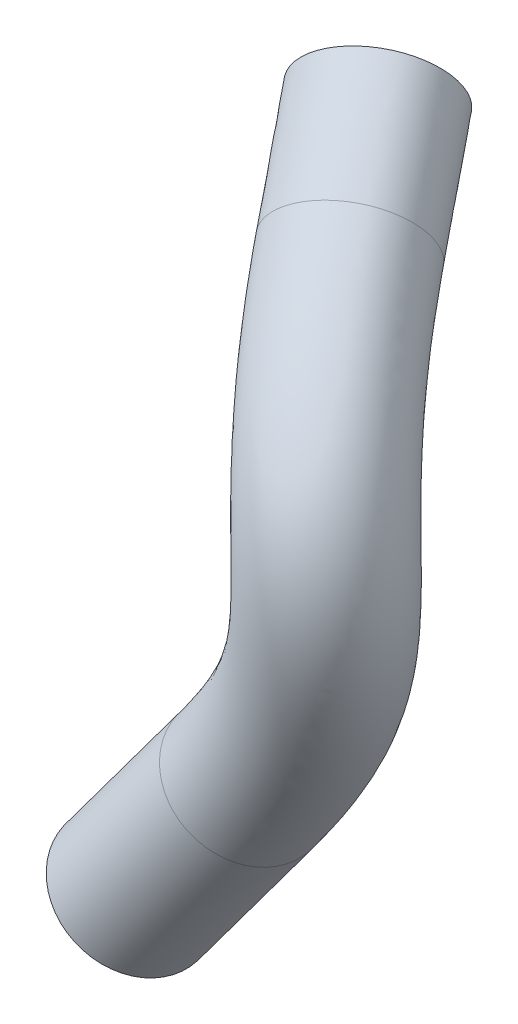
SolidWorks part; units mm, degrees
material "Silicon Rubber"
ref_plane "X-Y Datum" through (0, 0, 0) normal (0, 0, 1) x (1, 0, 0)
ref_plane "X-Z Datum" through (0, 0, 0) normal (0, 1, 0) x (1, 0, 0)
ref_plane "Y-Z Datum" through (0, 0, 0) normal (1, 0, 0) x (0, 0, -1)
sketch3d "3DSketch1"
  line L0 (202.8177, 305.3534, 24.6391) -> (225.5353, 335.9397, 24.6391)
  line L1 (229.5407, 421.9495, 7.7474) -> (216.3328, 432.7155, -11.0889)
  line L2 (229.5407, 421.9495, 7.7474) -> (216.3328, 432.7155, -11.0889) construction
  line L3 (229.0727, 422.3309, 7.08) -> (216.3328, 432.7155, -11.0889) construction
  line L4 (222.6956, 332.1164, 24.6391) -> (225.5353, 335.9397, 24.6391) construction
  circle A0 centre (222.6956, 332.1164, 24.6391) radius 12.3825 construction
  circle A4 centre (216.3328, 432.7155, -11.0889) radius 10 construction
  circle A5 centre (229.0727, 422.3309, 7.08) radius 7.8 construction
  circle A10 centre (225.5353, 335.9397, 24.6391) radius 6.985 construction
  circle A11 centre (216.3328, 432.7155, -11.0889) radius 10 construction
  circle A13 centre (229.0727, 422.3309, 7.08) radius 7.8 construction
  circle A14 centre (222.6956, 332.1164, 24.6391) radius 12.3825 construction
  circle A15 centre (225.5353, 335.9397, 24.6391) radius 6.985 construction
  spline S0 degree 3 poles (225.5353, 335.9397, 24.6391) (253.1384, 373.1037, 24.6391) (258.8518, 398.0571, 49.5494) (229.5407, 421.9495, 7.7474) knots 0 0 0 0 1 1 1 1
  point P6 (221.5328, 428.4769, -3.673)
  point P10 (233.1286, 419.0248, 12.8643)
  point P12 (221.5328, 428.4769, -3.673)
  point P14 (233.1286, 419.0248, 12.8643)
  point P16 (215.3124, 322.1759, 24.6391)
  point P19 (221.3704, 330.3322, 24.6391)
  point P21 (215.3124, 322.1759, 24.6391)
  point P24 (221.3704, 330.3322, 24.6391)
  dimension "D2" = 38.1
  dimension "D1" = 25.4
sweep "Sweep1" add path "3DSketch1" circular profile diameter 26.9875 parameters "D3"=26.9875
sweep "Cut-Sweep1" cut path "3DSketch1<2>" circular profile diameter 19.05 parameters "D3"=19.05
sketch3d "3DSketch1<2>" same geometry as "3DSketch1"
